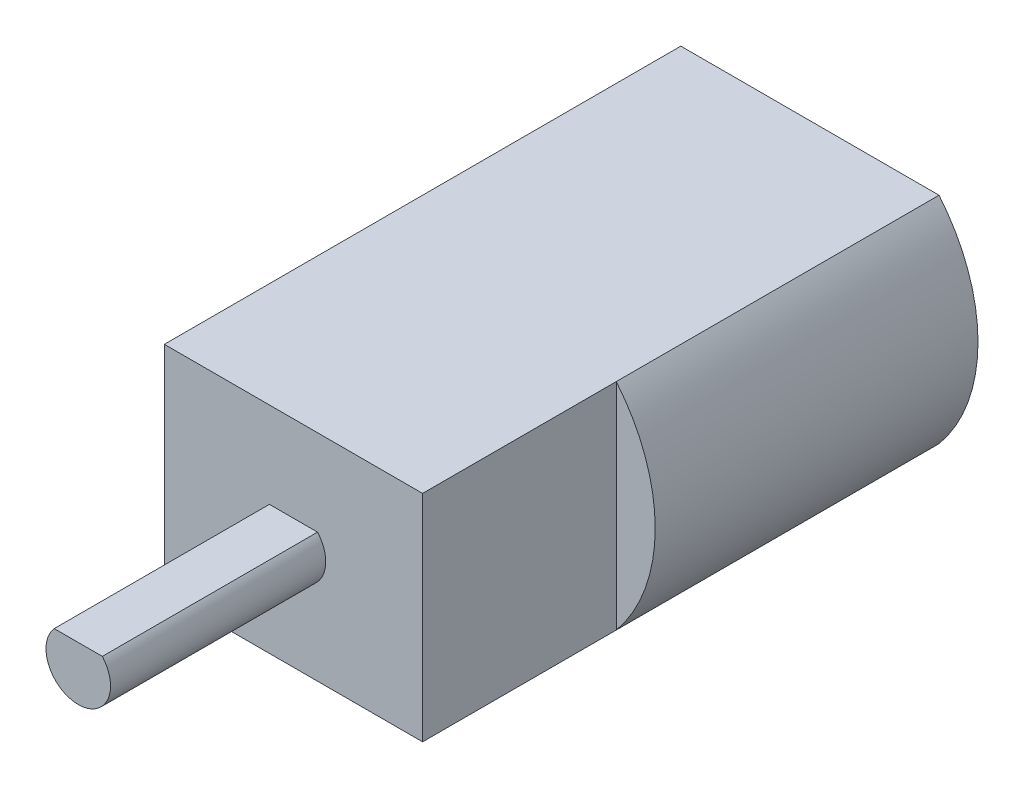
SolidWorks part; units mm, degrees
ref_plane "Front Plane" through (0, 0, 0) normal (0, 0, 1) x (1, 0, 0)
ref_plane "Top Plane" through (0, 0, 0) normal (0, 1, 0) x (1, 0, 0)
ref_plane "Right Plane" through (0, 0, 0) normal (1, 0, 0) x (0, 0, -1)
sketch "Sketch1" plane through (0, 0, 0) normal (0, 0, 1) x (1, 0, 0)
  line L0 (-6, 5) -> (6, 5)
  line L1 (-6, -5) -> (6, -5)
  circle A0 centre (0, 0) radius 2.5
  arc A2 (6, 5) -> (6, -5) centre (0, 0) cw
  arc A3 (-6, 5) -> (-6, -5) centre (0, 0) ccw
  point P7 (0, -5)
  point P8 (0, 5)
  point P9 (7.8102, 0)
  point P10 (-7.8102, 0)
  dimension "D1" = 5
  dimension "D2" = 12
  dimension "D3" = 10
extrude "Boss-Extrude1" add sketch "Sketch1" along normal blind 15 contours A3 L1 A2 L0
extrude "Boss-Extrude2" add sketch "Sketch1<3>" against normal blind 1 contours A0 region at (0, 0, 0)
sketch "Sketch1<3>" plane through (0, 0, 0) normal (0, 0, 1) x (1, 0, 0) same geometry as "Sketch1"
sketch "Sketch2" plane through (0, 0, 15) normal (0, 0, 1) x (1, 0, 0)
  line L1 (-6, 5) -> (6, 5)
  line L2 (-6, 5) -> (-6, -5)
  line L3 (-6, -5) -> (6, -5)
  line L4 (6, 5) -> (6, -5)
  point P4 (6, 0)
  point P6 (0, 5)
  dimension "D1" = 12
  dimension "D2" = 10
extrude "Boss-Extrude3" add sketch "Sketch2" along normal blind 9
sketch "Sketch3" plane through (0, 0, 24) normal (0, 0, 1) x (1, 0, 0)
  line L0 (-1.118, 1) -> (1.118, 1)
  arc A0 (1.118, 1) -> (-1.118, 1) centre (0, 0) cw
  dimension "D1" = 3
  dimension "D2" = 2.5
extrude "Boss-Extrude4" add sketch "Sketch3" along normal blind 10
